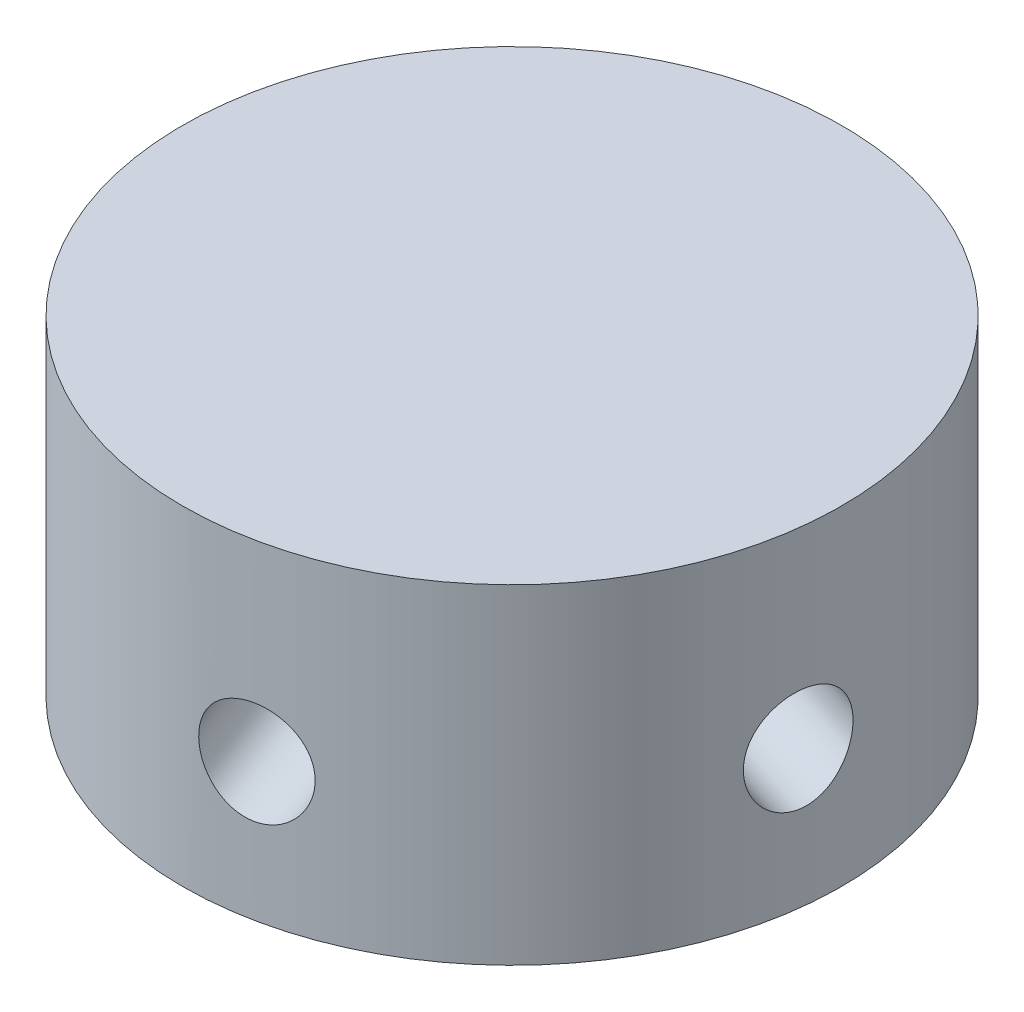
SolidWorks part; units mm, degrees
ref_plane "Front Plane" through (0, 0, 0) normal (0, 0, 1) x (1, 0, 0)
ref_plane "Top Plane" through (0, 0, 0) normal (0, 1, 0) x (1, 0, 0)
ref_plane "Right Plane" through (0, 0, 0) normal (1, 0, 0) x (0, 0, -1)
sketch "Sketch1" plane through (0, 0, 0) normal (0, 1, 0) x (1, 0, 0)
  circle A0 centre (0, 0) radius 10
  dimension "D1" = 20
extrude "Boss-Extrude1" add sketch "Sketch1" along normal blind 3 and the other way blind 7
ref_axis "5hubaxis" through (0, 5.5, 0) along (0, -1, 0)
ref_plane "holeplane" through (-3.3529, -1.0931, 1.8877) normal (0.8382, 0.2733, -0.4719) x (-0.4487, -0.1463, -0.8816)
sketch "Sketch4" plane through (-3.3529, -1.0931, 1.8877) normal (0.8382, 0.2733, -0.4719) x (-0.4487, -0.1463, -0.8816)
  circle A0 centre (0, 0) radius 1.5 construction
  circle A1 centre (0, 0) radius 1.5
extrude "hole" cut sketch "Sketch4" against normal through all
pattern_circular "holecir" count 5 over 360 about axis through (0, 5.5, 0) along (0, -1, 0) of "hole"
sketch "Sketch5" plane through (0, -7, 0) normal (0, -1, 0) x (1, 0, 0)
  line L0 (-10, 0) -> (10, 0) construction
  circle A0 centre (0, 0) radius 10 construction
  text T0 "5"
extrude "Boss-Extrude2" add sketch "Sketch5" along normal blind 1
